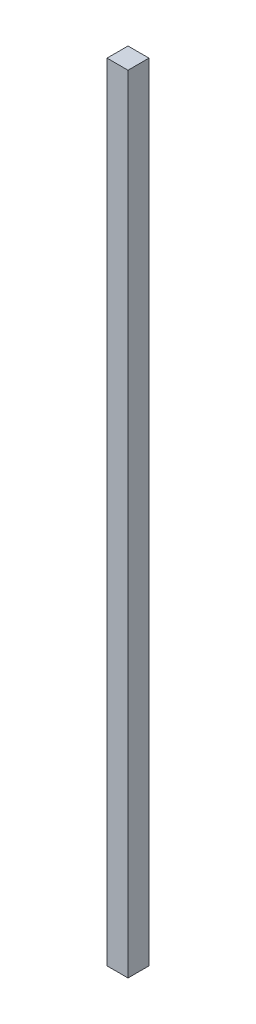
SolidWorks part; units mm, degrees
ref_plane "Front Plane" through (0, 0, 0) normal (0, 0, 1) x (1, 0, 0)
ref_plane "Top Plane" through (0, 0, 0) normal (0, 1, 0) x (1, 0, 0)
ref_plane "Right Plane" through (0, 0, 0) normal (1, 0, 0) x (0, 0, -1)
sketch "Sketch1" plane through (0, 0, 0) normal (0, 1, 0) x (1, 0, 0)
  line L1 (-2, 2) -> (2, 2)
  line L2 (-2, 2) -> (-2, -2)
  line L3 (-2, -2) -> (2, -2)
  line L4 (2, 2) -> (2, -2)
  line L5 (-2, 2) -> (2, -2) construction
  line L6 (-2, -2) -> (2, 2) construction
  point P0 (0, 0)
  dimension "D1" = 4
  dimension "D2" = 4
extrude "Boss-Extrude1" add sketch "Sketch1" along normal blind 150
sketch "Sketch2" plane through (0, 0, 0) normal (0, 0, 1) x (1, 0, 0)
  line L0 (0, 0) -> (0, 150) construction
  line L1 (-2, 150) -> (2, 150) construction
ref_axis "Axis1" through (0, 0, 0) along (0, 1, 0)
